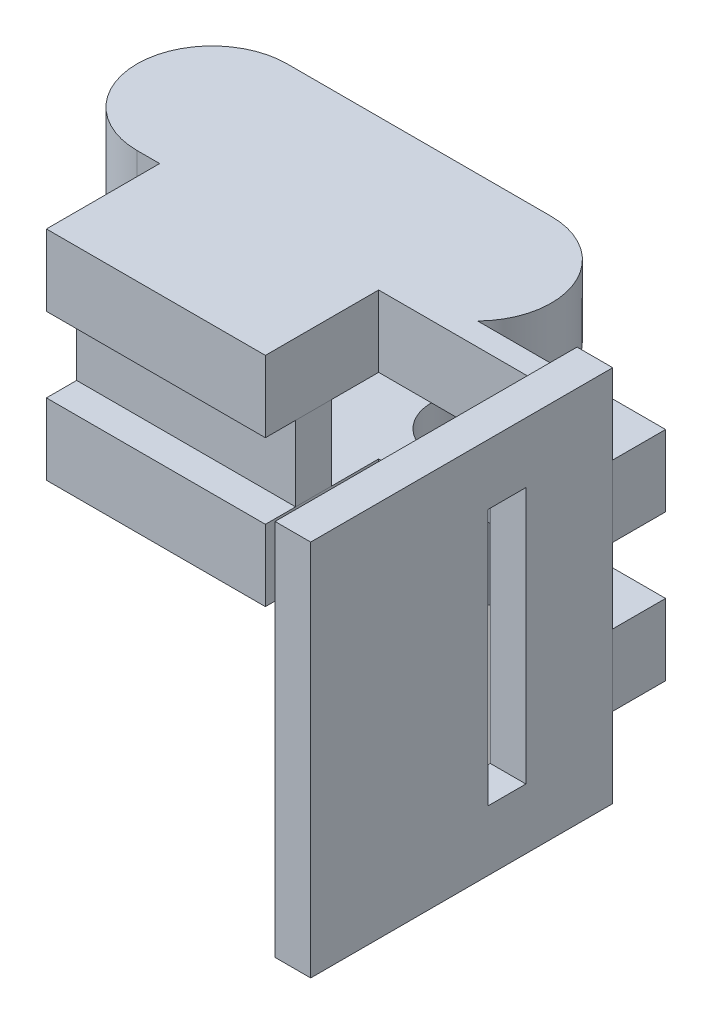
SolidWorks part; units mm, degrees
ref_plane "Front Plane" through (0, 0, 0) normal (0, 0, 1) x (1, 0, 0)
ref_plane "Top Plane" through (0, 0, 0) normal (0, 1, 0) x (1, 0, 0)
ref_plane "Right Plane" through (0, 0, 0) normal (1, 0, 0) x (0, 0, -1)
sketch "Sketch1" plane through (0, 0, 0) normal (0, 1, 0) x (1, 0, 0)
  line L0 (0, 12.6206) -> (44.45, 12.6206)
  line L1 (0, -12.6206) -> (3.81, -12.6206)
  line L2 (44.45, 0) -> (0, 0) construction
  line L3 (44.45, -12.6206) -> (40.64, -12.6206)
  line L4 (3.81, -12.6206) -> (3.81, -31.6706)
  line L5 (3.81, -31.6706) -> (40.64, -31.6706)
  line L6 (40.64, -31.6706) -> (40.64, -12.6206)
  line L7 (22.225, -26.5906) -> (22.225, -31.6706) construction
  line L8 (8.89, -20.5906) -> (35.56, -20.5906)
  line L9 (8.89, -20.5906) -> (8.89, -26.5906)
  line L10 (8.89, -26.5906) -> (35.56, -26.5906)
  line L11 (35.56, -20.5906) -> (35.56, -26.5906)
  circle A0 centre (0, 0) radius 4.7625
  circle A1 centre (0, 0) radius 7.5406
  circle A2 centre (44.45, 0) radius 4.7625
  circle A3 centre (44.45, 0) radius 7.5406
  arc A4 (0, -12.6206) -> (0, 12.6206) centre (0, 0) cw
  arc A5 (44.45, -12.6206) -> (44.45, 12.6206) centre (44.45, 0) ccw
  point P4 (40.64, -12.6206)
  dimension "D1" = 9.525
  dimension "D2" = 15.0812
  dimension "D4" = 5.08
  dimension "D3" = 44.45
  dimension "D5" = 3.81
  dimension "D6" = 19.05
  dimension "D7" = 6
  dimension "D8" = 5.08
  dimension "D9" = 5.08
extrude "Boss-Extrude1" add sketch "Sketch1" along normal blind 12 contours L3 A5 L0 A4 L1 L4 L5 L6 L8 L11 L10 L9 A1 A3 | A1 A0 | A3 A2 | L6 L3 A5 L0 A4 L1 L4 L5 region at (22.225, 0, 6.5106) region at (-7.3273, 0, 0) region at (37.1227, 0, 0)
extrude "Cut-Extrude1" cut sketch "Sketch1<3>" along normal blind 6 contours A3 | A1 | L9 L8 L11 L10
sketch "Sketch1<3>" plane through (0, 0, 0) normal (0, 1, 0) x (1, 0, 0) same geometry as "Sketch1"
ref_plane "Plane1" through (0, -6.3031, 0) normal (0, -1, 0) x (-1, 0, 0)
sketch "Sketch3" plane through (0, 0, 0) normal (0, -1, 0) x (1, 0, 0)
  line L0 (40.64, 31.6706) -> (40.64, 12.6206) construction
  line L1 (40.64, 31.6706) -> (40.64, 12.6206) construction
  line L3 (85.09, 12.6206) -> (85.09, 17.7006)
  line L4 (85.09, 17.7006) -> (79.09, 17.7006)
  line L5 (79.09, 17.7006) -> (79.09, 12.6206)
  line L6 (79.09, 12.6206) -> (40.64, 12.6206)
  line L7 (85.09, 12.6206) -> (85.09, 8.8106)
  line L8 (85.09, 8.8106) -> (40.64, 8.8106)
  line L9 (40.64, 8.8106) -> (40.64, 12.6206)
  point P6 (0, 0)
  point P8 (0, 0)
  dimension "D1" = 6
  dimension "D2" = 44.45
  dimension "D3" = 3.81
  dimension "D4" = 5.08
extrude "Boss-Extrude3" add sketch "Sketch3" against normal up to surface (12 mm away) up to face at (22.225, 12, 11.0728)
mirror "Mirror1" about plane through (0, -6.3031, 0) normal (0, -1, 0) of bodies 109 102
ref_plane "Plane2" through (0, 0, 20.5906) normal (0, 0, 1) x (1, 0, 0)
sketch "Sketch2" plane through (0, 0, 20.5906) normal (0, 0, 1) x (1, 0, 0)
  line L0 (35.56, -12.6063) -> (8.89, -12.6063) construction
  line L1 (8.89, -12.6063) -> (8.89, -18.6063) construction
  line L2 (8.89, -18.6063) -> (35.56, -18.6063) construction
  line L3 (35.56, -18.6063) -> (35.56, -12.6063) construction
  line L4 (8.89, 0) -> (35.56, 0) construction
  line L5 (35.56, 0) -> (35.56, 6) construction
  line L6 (35.56, 6) -> (8.89, 6) construction
  line L7 (8.89, 6) -> (8.89, 0) construction
  line L8 (35.56, -12.6063) -> (8.89, -12.6063) construction
  line L9 (8.89, -12.6063) -> (8.89, -18.6063)
  line L10 (8.89, -18.6063) -> (35.56, -18.6063)
  line L11 (35.56, -18.6063) -> (35.56, -12.6063)
  line L12 (8.89, 0) -> (35.56, 0) construction
  line L13 (35.56, 0) -> (35.56, 6)
  line L14 (35.56, 6) -> (8.89, 6)
  line L15 (8.89, 6) -> (8.89, 0)
  line L16 (3.81, 0) -> (40.64, 0) construction
  line L17 (3.81, -12.6063) -> (40.64, -12.6063) construction
  line L18 (3.81, 0) -> (40.64, 0) construction
  line L19 (3.81, -12.6063) -> (40.64, -12.6063) construction
  line L20 (40.64, -12.6063) -> (40.64, 0)
  line L21 (40.64, 0) -> (35.56, 0)
  line L22 (8.89, 0) -> (3.81, 0)
  line L23 (3.81, 0) -> (3.81, -12.6063)
  line L24 (3.81, -12.6063) -> (8.89, -12.6063)
  line L25 (35.56, -12.6063) -> (40.64, -12.6063)
extrude "Boss-Extrude2" add sketch "Sketch2" along normal up to surface (6 mm away) separate body up to face at (22.225, -15.6063, 26.5906)
sketch "Sketch4" plane through (85.09, 0, 0) normal (1, 0, 0) x (0, 0, -1)
  line L0 (-17.7006, -24.6063) -> (-17.7006, -12.6063) construction
  line L1 (-17.7006, 12) -> (-17.7006, 0) construction
  line L2 (-17.7006, -24.6063) -> (-17.7006, -12.6063) construction
  line L3 (-17.7006, 12) -> (-17.7006, 0) construction
  line L4 (-17.7006, 25.4469) -> (-17.7006, -38.0531)
  line L5 (-24.3602, -6.3031) -> (24.3602, -6.3031) construction
  line L6 (-17.7006, 25.4469) -> (-68.5006, 25.4469)
  line L7 (-68.5006, 25.4469) -> (-68.5006, -38.0531)
  line L8 (-68.5006, -38.0531) -> (-17.7006, -38.0531)
  line L14 (-38.6556, 15.2869) -> (-32.3056, 15.2869)
  line L15 (-38.6556, 15.2869) -> (-38.6556, -27.8931)
  line L16 (-38.6556, -27.8931) -> (-32.3056, -27.8931)
  line L17 (-32.3056, 15.2869) -> (-32.3056, -27.8931)
  line L18 (-38.6556, 15.2869) -> (-32.3056, -27.8931) construction
  line L19 (-38.6556, -27.8931) -> (-32.3056, 15.2869) construction
  point P6 (-35.4806, -6.3031)
  point P7 (-17.7006, -6.3031)
  dimension "D1" = 50.8
  dimension "D2" = 63.5
  dimension "D3" = 6.35
  dimension "D4" = 17.78
  dimension "D5" = 10.16
  dimension "D6" = 10.16
extrude "Boss-Extrude4" add sketch "Sketch4" against normal blind 6 separate body
